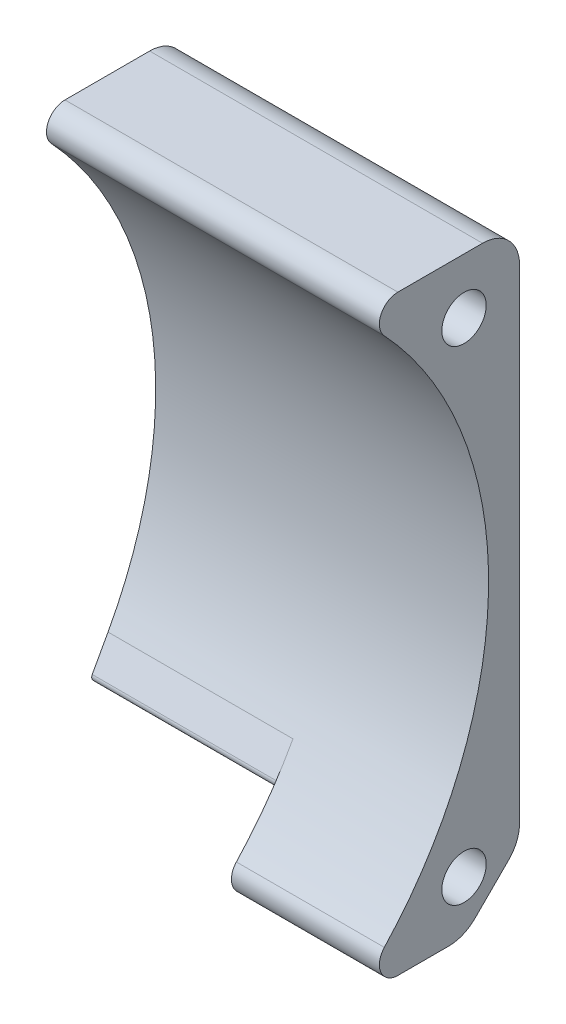
SolidWorks part; units mm, degrees
ref_plane "Front Plane" through (0, 0, 0) normal (0, 0, 1) x (1, 0, 0)
ref_plane "Top Plane" through (0, 0, 0) normal (0, 1, 0) x (1, 0, 0)
ref_plane "Right Plane" through (0, 0, 0) normal (1, 0, 0) x (0, 0, -1)
sketch "Sketch1" plane through (0, 0, 0) normal (1, 0, 0) x (0, 0, -1)
  line L0 (0, 0) -> (-14.3998, 0)
  line L1 (0, 0) -> (0, -50.8)
  line L3 (-3.175, 0) -> (-25.9073, 0) construction
  line L10 (-14.3998, -50.8) -> (0, -50.8)
  line L11 (-362.2224, -50.8) -> (-6.0776, -50.8) construction
  arc A0 (-14.3998, 0) -> (-14.3998, -50.8) centre (-35.9921, -25.4) cw
  arc A1 (-356.695, -2.6699) -> (-356.695, -48.1301) centre (-332.3079, -25.4) ccw construction
extrude "Boss-Extrude1" add sketch "Sketch1" along normal blind 28.575
chamfer "Chamfer1" distance 4.7625 angle 45 1 edges at (14.2875, -50.8, 0)
fillet "Fillet3" radius 3.175 2 edges at (14.2875, -50.8, 4.7625) (14.2875, -46.0375, 0)
sketch "Sketch2" plane through (28.575, 0, 0) normal (1, 0, 0) x (0, 0, -1)
  line L4 (-9.4322, -46.3099) -> (-6.748, -41.4053)
  line L5 (-14.3998, -50.8) -> (-6.0776, -50.8) construction
  line L6 (-14.3998, -50.8) -> (-6.0776, -50.8)
  line L7 (-3.8326, -49.8701) -> (-0.9299, -46.9674) construction
  line L8 (-0.0928, -46.3099) -> (-4.7625, -41.6401)
  line L9 (-4.7625, -50.9796) -> (-0.0928, -46.3099)
  line L10 (-9.4322, -46.3099) -> (-4.7625, -50.9796)
  line L11 (-4.7625, -41.6401) -> (-9.4322, -46.3099)
  line L12 (-0.3106, -46.092) -> (-4.7625, -41.6401)
  line L15 (-4.7625, -41.6401) -> (-9.4322, -46.3099)
  line L16 (-3.8326, -49.8701) -> (-0.9299, -46.9674)
  arc A0 (-14.3998, -50.8) -> (-14.3998, 0) centre (-35.9921, -25.4) ccw construction
  arc A1 (-14.3998, -50.8) -> (-6.748, -41.4053) centre (-35.9921, -25.4) ccw
  arc A2 (-6.0776, -50.8) -> (-3.8326, -49.8701) centre (-6.0776, -47.625) ccw construction
  arc A3 (-6.0776, -50.8) -> (-3.8326, -49.8701) centre (-6.0776, -47.625) ccw
  arc A4 (-0.9299, -46.9674) -> (0, -44.7224) centre (-3.175, -44.7224) ccw construction
  arc A5 (-0.9299, -46.9674) -> (-0.3106, -46.092) centre (-3.175, -44.7224) ccw
  dimension "D1" = 0.127
extrude "Cut-Extrude1" cut sketch "Sketch2" against normal through all from offset 12.7 offset against normal yes
fillet "Fillet4" radius 0.3969 1 edges at (7.9375, -46.3099, 9.4322)
fillet "Fillet5" radius 3.175 1 edges at (14.2875, 0, 0)
fillet "Fillet6" radius 1.5875 2 edges at (22.225, -50.8, 14.3998) (14.2875, 0, 14.3998)
sketch "Sketch3" plane through (28.575, 0, 0) normal (1, 0, 0) x (0, 0, -1)
  line L0 (-3.175, 0) -> (-10.4437, 0) construction
  line L1 (0, -44.7224) -> (0, -3.175) construction
  circle A0 centre (-4.7625, -4.7625) radius 4.7625 construction
  circle A1 centre (-4.7625, -4.7625) radius 1.905
  circle A2 centre (-4.7625, -46.3099) radius 1.905
  circle A3 centre (-4.7625, -46.3099) radius 1.651 construction
  dimension "D1" = 9.525
  dimension "D2" = 3.81
  dimension "D3" = 3.81
extrude "Cut-Extrude2" cut sketch "Sketch3" against normal through all
